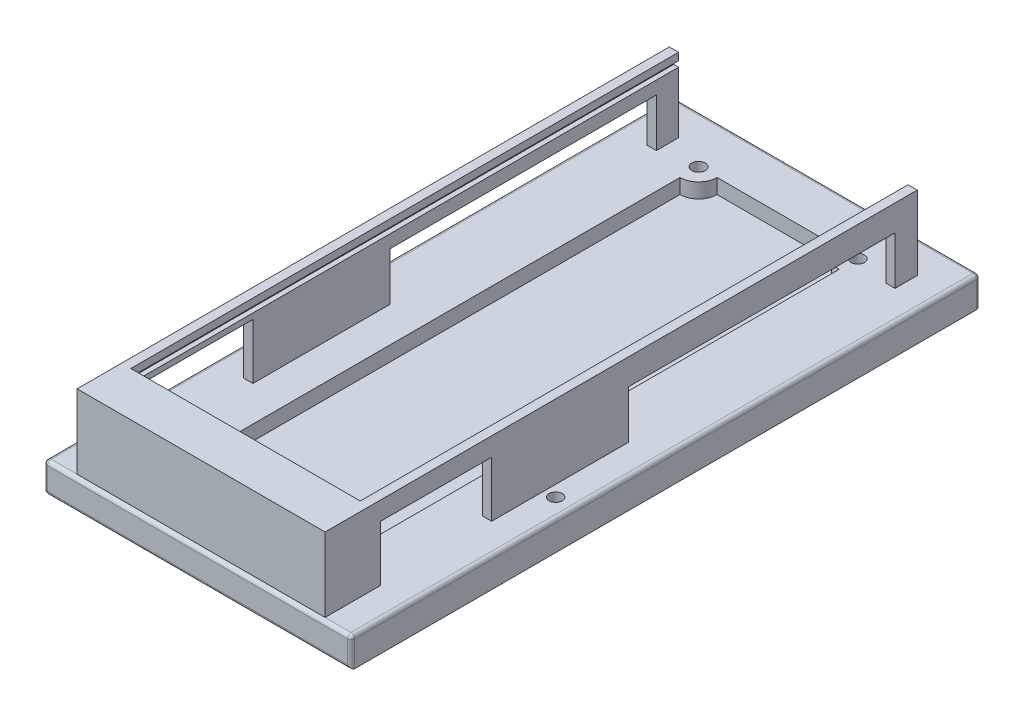
SolidWorks part; units mm, degrees
ref_plane "Front Plane" through (0, 0, 0) normal (0, 0, 1) x (1, 0, 0)
ref_plane "Top Plane" through (0, 0, 0) normal (0, 1, 0) x (1, 0, 0)
ref_plane "Right Plane" through (0, 0, 0) normal (1, 0, 0) x (0, 0, -1)
sketch "Sketch1" plane through (0, 0, 0) normal (0, 1, 0) x (1, 0, 0)
  line L0 (41.5, 95) -> (41.5, 0) construction
  line L1 (0, 0) -> (83, 0)
  line L2 (0, 0) -> (0, 170)
  line L3 (0, 170) -> (83, 170)
  line L4 (83, 0) -> (83, 170)
  line L5 (20, 156.9) -> (20, 13.1) construction
  circle A0 centre (5, 60.3) radius 1.75
  circle A1 centre (20, 13.1) radius 1.65 construction
  circle A2 centre (20, 156.9) radius 1.65 construction
  circle A3 centre (78, 60.3) radius 1.75
  circle A4 centre (63, 13.1) radius 1.65 construction
  circle A5 centre (63, 156.9) radius 1.65 construction
  point P19 (20, 85)
  point P20 (41.5, 0)
  point P21 (0, 85)
  dimension "D2" = 36.5
  dimension "D3" = 3.5
  dimension "D5" = 47.2
  dimension "D6" = 21.5
  dimension "D7" = 3.3
  dimension "D9" = 143.8
  dimension "D10" = 3.3
  dimension "D1" = 83
  dimension "D4" = 170
extrude "Boss-Extrude1" add sketch "Sketch1" along normal blind 8
sketch "Sketch3" plane through (0, 0, 0) normal (0, -1, 0) x (1, 0, 0)
  point P0 (20, -13.1)
  point P1 (63, -13.1)
  point P3 (63, -156.9)
  point P5 (20, -156.9)
hole_wizard "CBORE for M3 SHCS1" positions "Sketch3" profile "Sketch4" counterbore size "M3" standard "ANSI Metric" end condition through all
sketch "Sketch4" plane through (20, 0, -13.1) normal (1, 0, 0) x (0, 0, -1)
  line L0 (0, 0) -> (0, 8)
  line L1 (0, 8) -> (1.8, 8)
  line L3 (1.8, 8) -> (1.8, 3)
  line L4 (1.8, 3) -> (3.25, 3)
  line L5 (3.25, 3) -> (3.25, 0)
  line L7 (3.25, 0) -> (0, 0)
  line L11 (0, -6.35) -> (0, 107.95) construction
  dimension "Thru Hole Dia." = 3.6
  dimension "Thru Hole Depth" = 8
  dimension "C'Bore Dia." = 6.5
  dimension "C'Bore Depth" = 3
sketch "Sketch5" plane through (0, 8, 0) normal (0, 1, 0) x (1, 0, 0)
  line L5 (25, 156.9) -> (58, 156.9)
  line L6 (20, 151.9) -> (20, 18.1)
  line L11 (25, 13.1) -> (58, 13.1)
  line L12 (63, 151.9) -> (63, 18.1)
  arc A0 (20, 151.9) -> (25, 156.9) centre (20, 156.9) ccw
  arc A1 (58, 156.9) -> (63, 151.9) centre (63, 156.9) ccw
  arc A2 (63, 18.1) -> (58, 13.1) centre (63, 13.1) ccw
  arc A7 (25, 13.1) -> (20, 18.1) centre (20, 13.1) ccw
  point P0 (20, 156.9)
  point P1 (63, 156.9)
  point P2 (63, 13.1)
  point P3 (20, 13.1)
extrude "Cut-Extrude1" cut sketch "Sketch5" against normal blind 4
sketch "Sketch6" plane through (0, 0, 0) normal (0, -1, 0) x (1, 0, 0)
  line L1 (17, -95) -> (22, -95)
  line L2 (17, -95) -> (17, -115)
  line L3 (17, -115) -> (22, -115)
  line L4 (22, -95) -> (22, -115)
  dimension "D1" = 5
  dimension "D2" = 20
  dimension "D3" = 3
  dimension "D4" = 34.7
extrude "Boss-Extrude2" add sketch "Sketch6" along normal blind 8.8
sketch "Sketch7" plane through (0, 0, -115) normal (0, 0, -1) x (-1, 0, 0)
  line L0 (-22, -8.8) -> (-22, 0) construction
  line L1 (-17, 0) -> (-20.2, 0)
  line L2 (-17, 0) -> (-17, -6.8)
  line L3 (-17, -6.8) -> (-20.2, -6.8)
  line L4 (-20.2, 0) -> (-20.2, -6.8)
  dimension "D1" = 6.8
  dimension "D2" = 1.8
extrude "Cut-Extrude2" cut sketch "Sketch7" against normal through all
fillet "Fillet1" radius 6 1 edges at (22, 0, -105) second distance 8 first distance on face at (20, 0, -16.35)
fillet "Fillet2" radius 1 10 edges at (0, 4, 0) (41.5, 8, 0) (83, 4, 0) (83, 4, -170) (83, 8, -85) (41.5, 8, -170) (0, 4, -170) (0, 8, -85) (0, 0, -85) (41.5, 0, 0)
sketch "Sketch8" plane through (0, 8, 0) normal (0, 1, 0) x (1, 0, 0)
  line L1 (8, 161) -> (75, 161)
  line L2 (8, 161) -> (8, 1)
  line L3 (8, 1) -> (75, 1)
  line L4 (75, 161) -> (75, 1)
  line L6 (1, 1) -> (82, 1) construction
  circle A4 centre (5, 60.3) radius 1.75 construction
  dimension "D1" = 3
  dimension "D3" = 160
  dimension "D2" = 3
  dimension "D4" = 0
extrude "Boss-Extrude4" add sketch "Sketch8" along normal blind 20
sketch "Sketch11" plane through (0, 0, -161) normal (0, 0, -1) x (-1, 0, 0)
  line L0 (-75, 8) -> (-8, 8) construction
  line L1 (-72.5, 8) -> (-10.5, 8)
  line L2 (-72.5, 8) -> (-72.5, 24.5)
  line L3 (-72.5, 28) -> (-10.5, 28)
  line L4 (-10.5, 8) -> (-10.5, 24.5)
  line L5 (-75, 28) -> (-75, 8) construction
  line L6 (-8, 28) -> (-8, 8) construction
  line L7 (-75, 28) -> (-8, 28) construction
  line L8 (-10.5, 24.5) -> (-9.2, 24.5)
  line L9 (-73.8, 26) -> (-72.5, 26)
  line L10 (-73.8, 26) -> (-73.8, 24.5)
  line L11 (-73.8, 24.5) -> (-72.5, 24.5)
  line L12 (-9.2, 26) -> (-9.2, 24.5)
  line L13 (-10.5, 26) -> (-9.2, 26)
  line L14 (-72.5, 26) -> (-72.5, 28)
  line L15 (-10.5, 26) -> (-10.5, 28)
  dimension "D1" = 2.5
  dimension "D2" = 2.5
  dimension "D3" = 0
  dimension "D4" = 1.2
  dimension "D5" = 1.5
  dimension "D6" = 1.2
  dimension "D7" = 2
extrude "Cut-Extrude3" cut sketch "Sketch11" against normal blind 148
sketch "Sketch12" plane through (0, 0, -13) normal (0, 0, -1) x (-1, 0, 0)
  line L1 (-73.8, 26) -> (-9.2, 26)
  line L2 (-73.8, 26) -> (-73.8, 24.5)
  line L3 (-73.8, 24.5) -> (-9.2, 24.5)
  line L4 (-9.2, 26) -> (-9.2, 24.5)
extrude "Cut-Extrude4" cut sketch "Sketch12" against normal blind 1
sketch "Sketch15" plane through (75, 0, 0) normal (1, 0, 0) x (0, 0, -1)
  line L0 (1, 8) -> (169, 8) construction
  line L1 (128, 8) -> (110, 8)
  line L2 (128, 8) -> (128, 21) construction
  line L3 (128, 21) -> (110, 21)
  line L4 (110, 8) -> (110, 21) construction
  line L5 (101, 21) -> (110, 21)
  line L6 (1, 8) -> (161, 8) construction
  line L7 (101, 8) -> (83, 8)
  line L8 (101, 8) -> (101, 21) construction
  line L9 (101, 21) -> (83, 21)
  line L10 (83, 8) -> (83, 21)
  line L12 (101, 8) -> (110, 8)
  line L13 (128, 21) -> (137, 21)
  line L14 (137, 21) -> (155, 21)
  line L15 (137, 21) -> (137, 8) construction
  line L16 (137, 8) -> (155, 8)
  line L17 (155, 21) -> (155, 8)
  line L18 (128, 8) -> (137, 8)
  line L20 (161, 28) -> (161, 8) construction
  dimension "D1" = 18
  dimension "D2" = 13
  dimension "D3" = 6
  dimension "D4" = 18
  dimension "D5" = 13
  dimension "D6" = 9
  dimension "D7" = 18
  dimension "D8" = 13
  dimension "D9" = 9
extrude "Cut-Extrude5" cut sketch "Sketch15" against normal through all and the other way through all
sketch "Sketch16" plane through (75, 0, 0) normal (1, 0, 0) x (0, 0, -1)
  line L0 (1, 8) -> (169, 8) construction
  line L1 (16, 8) -> (46, 8)
  line L2 (16, 8) -> (16, 23)
  line L3 (16, 23) -> (46, 23)
  line L4 (46, 8) -> (46, 23)
  line L5 (1, 28) -> (1, 8) construction
  point P8 (16, 15.5)
  dimension "D1" = 15
  dimension "D2" = 30
  dimension "D3" = 15
extrude "Cut-Extrude6" cut sketch "Sketch16" against normal through all
